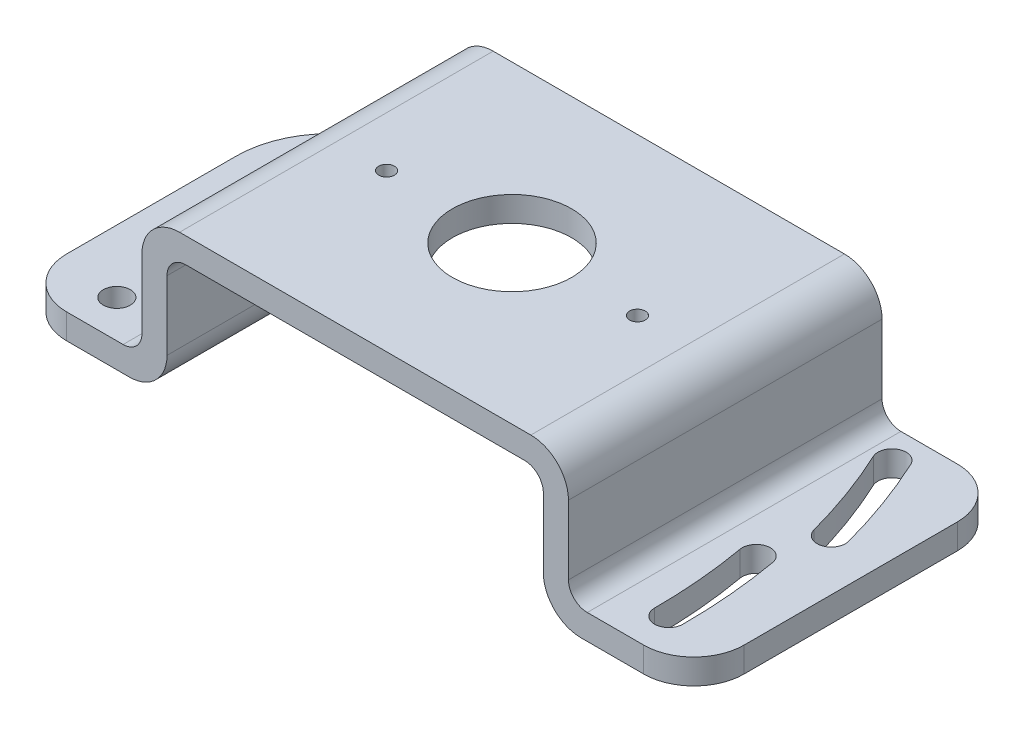
SolidWorks part; units mm, degrees
ref_plane "Front Plane" through (0, 0, 0) normal (0, 0, 1) x (1, 0, 0)
ref_plane "Top Plane" through (0, 0, 0) normal (0, 1, 0) x (1, 0, 0)
ref_plane "Right Plane" through (0, 0, 0) normal (1, 0, 0) x (0, 0, -1)
ref_axis "X" through (-88.99, 0, 0) along (1, 0, 0)
ref_axis "Y" through (0, 0, -88.99) along (0, 0, 1)
ref_axis "Z" through (0, 55, 0) along (0, -1, 0)
sketch "Sketch1" plane through (0, 0, 0) normal (0, 0, 1) x (1, 0, 0)
  line L0 (-54, 0) -> (-30, 0)
  line L1 (-30, 0) -> (-30, 20)
  line L2 (-30, 20) -> (30, 20)
  line L3 (30, 20) -> (30, 0)
  line L4 (30, 0) -> (54, 0)
  line L5 (54, 0) -> (54, 4)
  line L6 (54, 4) -> (34, 4)
  line L7 (34, 4) -> (34, 24)
  line L8 (34, 24) -> (-34, 24)
  line L9 (-34, 24) -> (-34, 4)
  line L10 (-34, 4) -> (-54, 4)
  line L11 (-54, 4) -> (-54, 0)
  line L12 (0, 0) -> (0, 20) construction
  line L13 (0, 20) -> (0, 24) construction
  dimension "D1" = 60
  dimension "D2" = 4
  dimension "D3" = 20
  dimension "D4" = 4
  dimension "D5" = 4
  dimension "D6" = 20
extrude "Boss-Extrude1" add sketch "Sketch1" along normal blind 50
sketch "Sketch2" plane through (0, 24, 0) normal (0, 1, 0) x (1, 0, 0)
  line L0 (-54, -25) -> (0, -25) construction
  line L1 (-54, -50) -> (-54, 0) construction
  line L2 (0, -25) -> (0, 0) construction
  circle A0 centre (0, -25) radius 9.5
  dimension "D1" = 19
extrude "Cut-Extrude1" cut sketch "Sketch2" against normal blind 10
hole_wizard "M3 Tapped Hole1" positions "Sketch5" profile "Sketch6" tap size "M3" standard "DIN" end condition through all
sketch "Sketch5" plane through (0, 24, 0) normal (0, 1, 0) x (1, 0, 0)
  line L0 (0, -25) -> (-20, -25) construction
  line L3 (0, -25) -> (20, -25) construction
  point P2 (-20, -25)
  point P8 (20, -25)
  dimension "D1" = 20
sketch "Sketch6" plane through (20, 24, 25) normal (1, 0, 0) x (0, 0, 1)
  line L0 (0, 0) -> (0, 24)
  line L1 (0, 24) -> (1.25, 24)
  line L2 (1.25, 24) -> (1.25, 0)
  line L5 (1.25, 0) -> (0, 0)
  line L11 (0, -6.35) -> (0, 107.95) construction
  dimension "Thread Major Dia." = 2.5
  dimension "Thru Tap Drill Depth" = 24
sketch "Sketch7" plane through (0, 4, 0) normal (0, 1, 0) x (1, 0, 0)
  line L0 (-54, -50) -> (-54, 0) construction
  line L1 (-34, -50) -> (-54, -50) construction
  line L2 (-44, -44) -> (43.6651, -36.3303) construction
  line L3 (43.6651, -36.3303) -> (-44, -44) construction
  line L4 (-44, -44) -> (43.3914, -12.1921) construction
  line L5 (-44, -44) -> (-44, 7.0995) construction
  circle A0 centre (-44, -44) radius 2.15
  arc A1 (44, -44) -> (42.6631, -28.719) centre (-44, -44) ccw construction
  arc A2 (46.25, -44) -> (44.8789, -28.3283) centre (-44, -44) ccw
  arc A3 (41.75, -44) -> (40.4473, -29.1097) centre (-44, -44) ccw
  arc A4 (41.75, -44) -> (46.25, -44) centre (44, -44) ccw
  arc A5 (44.8789, -28.3283) -> (40.4473, -29.1097) centre (42.6631, -28.719) ccw
  arc A6 (45.8311, -19.9298) -> (40.2866, -4.6965) centre (-44, -44) ccw construction
  arc A7 (48.0044, -19.3475) -> (42.3258, -3.7456) centre (-44, -44) ccw
  arc A8 (43.6578, -20.5122) -> (38.2474, -5.6474) centre (-44, -44) ccw
  arc A9 (43.6578, -20.5122) -> (48.0044, -19.3475) centre (45.8311, -19.9298) ccw
  arc A10 (42.3258, -3.7456) -> (38.2474, -5.6474) centre (40.2866, -4.6965) ccw
  point P8 (43.6651, -36.3303)
  point P13 (43.3914, -12.1921)
  dimension "D1" = 4.3
  dimension "D5" = 2.25
  dimension "D6" = 2.25
  dimension "D8" = 10
  dimension "D2" = 10
  dimension "D3" = 6
  dimension "D4" = 88
  dimension "D7" = 93
  dimension "D9" = 10
  dimension "D10" = 85
  dimension "D11" = 70
extrude "Cut-Extrude2" cut sketch "Sketch7" against normal blind 10
fillet "Fillet1" radius 3 4 edges at (34, 4, 25) (30, 20, 25) (-30, 20, 25) (-34, 4, 25)
fillet "Fillet2" radius 6 4 edges at (30, 0, 25) (34, 24, 25) (-30, 0, 25) (-34, 24, 25)
fillet "Fillet3" radius 15 1 edges at (-54, 2, 0)
fillet "Fillet4" radius 8 3 edges at (-54, 2, 50) (54, 2, 50) (54, 2, 0)
